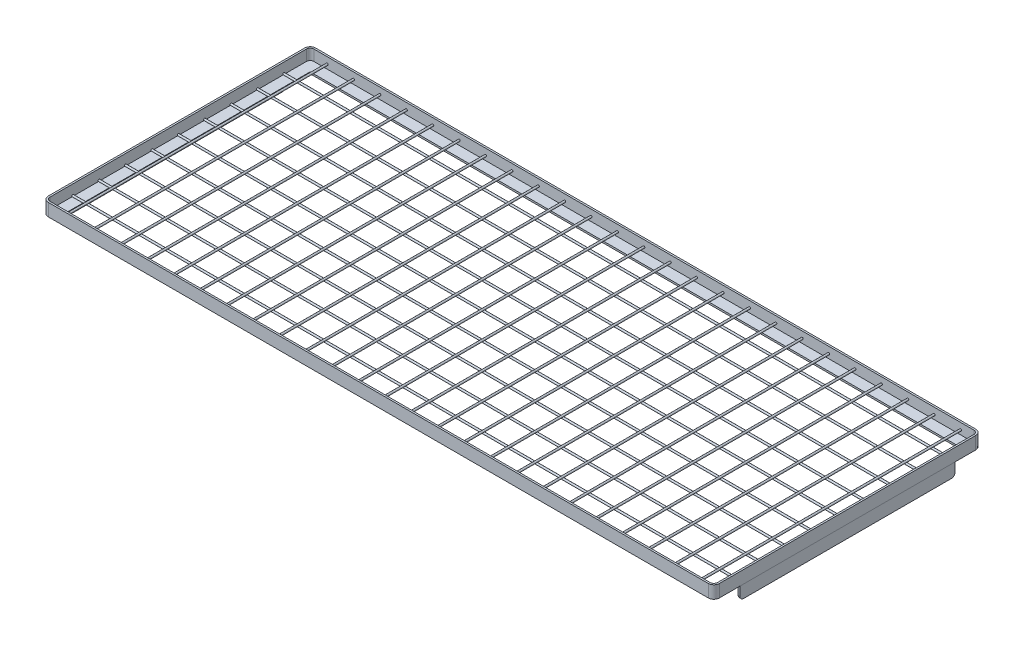
SolidWorks part; units mm, degrees
ref_plane "Front Plane" through (0, 0, 0) normal (0, 0, 1) x (1, 0, 0)
ref_plane "Top Plane" through (0, 0, 0) normal (0, 1, 0) x (1, 0, 0)
ref_plane "Right Plane" through (0, 0, 0) normal (1, 0, 0) x (0, 0, -1)
sketch "Sketch1" plane through (0, 0, 0) normal (0, 1, 0) x (1, 0, 0)
  line L0 (-667.0675, -270.256) -> (667.0675, -270.256)
  line L1 (-667.0675, -266.7) -> (667.0675, -266.7)
  line L2 (-674.6875, -259.08) -> (-674.6875, 259.08)
  line L3 (-667.0675, 266.7) -> (667.0675, 266.7)
  line L4 (674.6875, -259.08) -> (674.6875, 259.08)
  line L5 (678.2435, -259.08) -> (678.2435, 259.08)
  line L6 (-667.0675, 270.256) -> (667.0675, 270.256)
  line L7 (-678.2435, -259.08) -> (-678.2435, 259.08)
  arc A0 (-667.0675, 266.7) -> (-674.6875, 259.08) centre (-667.0675, 259.08) ccw
  arc A1 (-674.6875, -259.08) -> (-667.0675, -266.7) centre (-667.0675, -259.08) ccw
  arc A2 (667.0675, -266.7) -> (674.6875, -259.08) centre (667.0675, -259.08) ccw
  arc A3 (674.6875, 259.08) -> (667.0675, 266.7) centre (667.0675, 259.08) ccw
  arc A4 (667.0675, -270.256) -> (678.2435, -259.08) centre (667.0675, -259.08) ccw
  arc A5 (678.2435, 259.08) -> (667.0675, 270.256) centre (667.0675, 259.08) ccw
  arc A6 (-667.0675, 270.256) -> (-678.2435, 259.08) centre (-667.0675, 259.08) ccw
  arc A7 (-678.2435, -259.08) -> (-667.0675, -270.256) centre (-667.0675, -259.08) ccw
  point P0 (0, 0)
  dimension "D1" = 1349.375
  dimension "D2" = 533.4
  dimension "D3" = 3.556
extrude "Boss-Extrude1" add sketch "Sketch1" along normal blind 21.844
sketch "Sketch3" plane through (0, 0, 0) normal (0, -1, 0) x (1, 0, 0)
  line L0 (652.8435, 244.856) -> (652.8435, -244.856)
  line L1 (-667.0675, 270.256) -> (667.0675, 270.256)
  line L2 (-678.2435, 259.08) -> (-678.2435, -259.08)
  line L3 (-667.0675, -270.256) -> (667.0675, -270.256)
  line L4 (678.2435, 259.08) -> (678.2435, -259.08)
  line L5 (-678.2435, 270.256) -> (678.2435, -270.256) construction
  line L6 (-678.2435, -270.256) -> (673.3657, 268.3123) construction
  line L7 (-652.8435, -244.856) -> (652.8435, -244.856)
  line L8 (-652.8435, 244.856) -> (-652.8435, -244.856)
  line L9 (-652.8435, 244.856) -> (652.8435, 244.856)
  line L10 (-678.2435, 270.256) -> (678.2435, 270.256) construction
  line L11 (678.2435, 270.256) -> (678.2435, -270.256) construction
  line L12 (-678.2435, -270.256) -> (678.2435, -270.256) construction
  line L13 (-678.2435, 270.256) -> (-678.2435, -270.256) construction
  arc A0 (678.2435, 259.08) -> (667.0675, 270.256) centre (667.0675, 259.08) ccw
  arc A1 (667.0675, -270.256) -> (678.2435, -259.08) centre (667.0675, -259.08) ccw
  arc A2 (-678.2435, -259.08) -> (-667.0675, -270.256) centre (-667.0675, -259.08) ccw
  arc A3 (-667.0675, 270.256) -> (-678.2435, 259.08) centre (-667.0675, 259.08) ccw
  point P0 (0, 0)
  dimension "D1" = 25.4
extrude "Boss-Extrude2" add sketch "Sketch3" along normal blind 3.556
sketch "Sketch10" plane through (-674.6875, 0, 0) normal (1, 0, 0) x (0, 0, -1)
  line L1 (-259.08, -3.556) -> (259.08, -3.556) construction
  circle A0 centre (0, 1.524) radius 1.905
  dimension "D1" = 3.81
  dimension "D2" = 5.08
  dimension "D3" = 259.08
extrude "Boss-Extrude13" add sketch "Sketch10" along normal up to next
pattern_linear "LPattern1" count 5 spacing 53.34 along (0, 0, 1) count 5 spacing 53.34 along (0, 0, -1) of "Boss-Extrude13"
sketch "Sketch8" plane through (-678.2435, 0, 0) normal (-1, 0, 0) x (0, 0, 1)
  line L0 (-259.08, 21.844) -> (259.08, -3.556) construction
  line L1 (259.08, -3.556) -> (-259.08, -3.556) construction
  line L2 (0, 9.144) -> (0, -113.0774) construction
  line L4 (-217.4875, -28.956) -> (217.4875, -28.956)
  line L5 (-217.4875, -28.956) -> (-217.4875, -3.556)
  line L6 (-217.4875, -3.556) -> (217.4875, -3.556)
  line L7 (217.4875, -28.956) -> (217.4875, -3.556)
  line L8 (-217.4875, -28.956) -> (217.4875, -3.556) construction
  line L9 (-217.4875, -3.556) -> (217.4875, -28.956) construction
  point P8 (0, -16.256)
  dimension "D1" = 434.975
  dimension "D2" = 25.4
extrude "Boss-Extrude11" add sketch "Sketch8" against normal blind 3.556 separate body
sketch "Sketch11" plane through (0, 0, 266.7) normal (0, 0, -1) x (-1, 0, 0)
  line L0 (667.0675, 0) -> (-667.0675, 0) construction
  circle A0 centre (0, 8.89) radius 1.905
  dimension "D1" = 3.81
  dimension "D2" = 8.89
extrude "Boss-Extrude14" add sketch "Sketch11" along normal up to next
pattern_linear "LPattern2" count 13 spacing 53.34 along (-1, 0, 0) count 13 spacing 53.34 along (1, 0, 0) of "Boss-Extrude14"
sketch "Sketch9" plane through (678.2435, 0, 0) normal (1, 0, 0) x (0, 0, -1)
  line L0 (0, -3.556) -> (0, -163.5002) construction
  line L1 (-217.4875, -3.556) -> (217.4875, -3.556) construction
  line L2 (259.08, -3.556) -> (-259.08, -3.556) construction
  line L3 (-217.4875, -28.956) -> (217.4875, -28.956)
  line L4 (-217.4875, -28.956) -> (-217.4875, -3.556)
  line L5 (-217.4875, -3.556) -> (217.4875, -3.556)
  line L6 (217.4875, -28.956) -> (217.4875, -3.556)
  line L7 (-217.4875, -28.956) -> (217.4875, -3.556) construction
  line L8 (-217.4875, -3.556) -> (217.4875, -28.956) construction
  point P5 (0, -16.256)
  dimension "D1" = 25.4
  dimension "D2" = 434.975
extrude "Boss-Extrude12" add sketch "Sketch9" against normal blind 3.556 separate body
fillet "Fillet1" radius 7.62 2 edges at (-676.4655, -28.956, 217.4875) (-676.4655, -28.956, -217.4875)
fillet "Fillet2" radius 7.62 2 edges at (676.4655, -28.956, -217.4875) (676.4655, -28.956, 217.4875)
